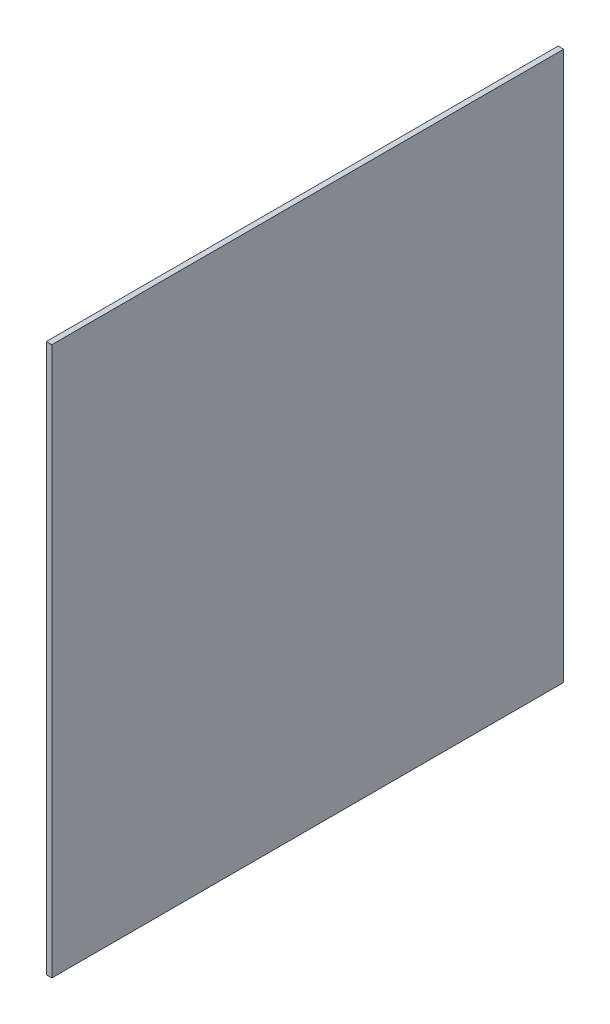
SolidWorks part; units mm, degrees
ref_plane "Front Plane" through (0, 0, 0) normal (0, 0, 1) x (1, 0, 0)
ref_plane "Top Plane" through (0, 0, 0) normal (0, 1, 0) x (1, 0, 0)
ref_plane "Right Plane" through (0, 0, 0) normal (1, 0, 0) x (0, 0, -1)
sketch "Sketch1" plane through (0, 0, 0) normal (1, 0, 0) x (0, 0, -1)
  line L1 (-268.1452, 16.0645) -> (11.8548, 16.0645)
  line L2 (-268.1452, 16.0645) -> (-268.1452, -283.9355)
  line L3 (-268.1452, -283.9355) -> (11.8548, -283.9355)
  line L4 (11.8548, 16.0645) -> (11.8548, -283.9355)
  dimension "D1" = 300
  dimension "D2" = 280
extrude "Boss-Extrude2" add sketch "Sketch1" along normal blind 3
